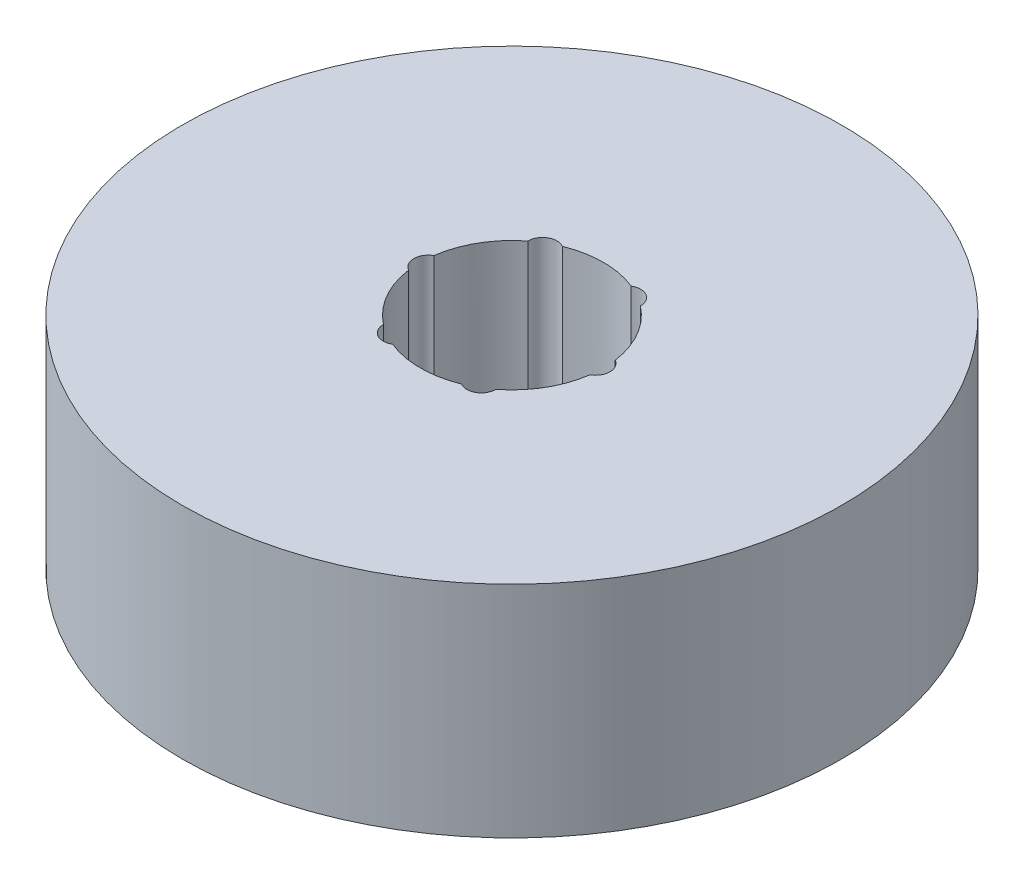
SolidWorks part; units mm, degrees
ref_plane "Front Plane" through (0, 0, 0) normal (0, 0, 1) x (1, 0, 0)
ref_plane "Top Plane" through (0, 0, 0) normal (0, 1, 0) x (1, 0, 0)
ref_plane "Right Plane" through (0, 0, 0) normal (1, 0, 0) x (0, 0, -1)
sketch "Sketch1" plane through (0, 0, 0) normal (0, 1, 0) x (1, 0, 0)
  circle A0 centre (0, 0) radius 45
  dimension "FLANGE_OD" = 90
extrude "Boss-Extrude1" add sketch "Sketch1" along normal blind 30
sketch "Sketch2" plane through (0, 0, 0) normal (0, 1, 0) x (1, 0, 0)
  circle A0 centre (0, 0) radius 12.5
  dimension "BORE_D" = 25
extrude "Cut-Extrude1" cut sketch "Sketch2" along normal through all
sketch "Sketch3" plane through (0, 30, 0) normal (0, 1, 0) x (1, 0, 0)
  circle A0 centre (0, 0) radius 11.4244 construction
  circle A1 centre (-11.4244, 0) radius 1.9686
  dimension "BOLT_D" = 3.9373
  dimension "BOLT_PCD" = 22.8489
extrude "Cut-Extrude2" cut sketch "Sketch3" against normal blind 23.7658
pattern_circular "CirPattern1" count 6 over 360 about axis through (0, 0, 0) along (0, 1, 0) of "Cut-Extrude2"
